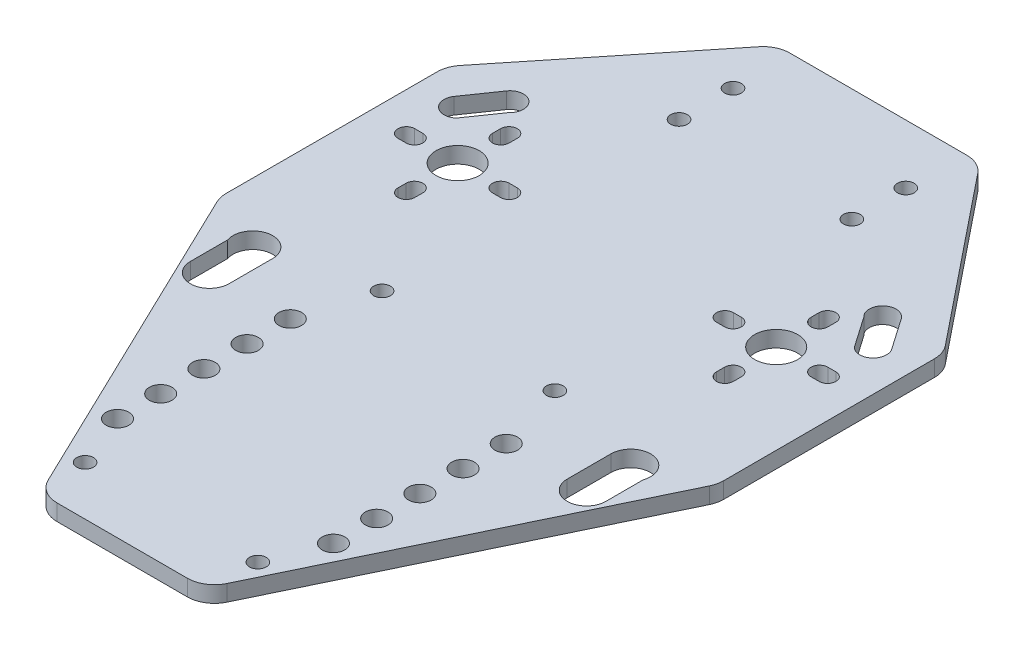
SolidWorks part; units mm, degrees
material "Thornel Mat VMA"
ref_plane "Front Plane" through (0, 0, 0) normal (0, 0, 1) x (1, 0, 0)
ref_plane "Top Plane" through (0, 0, 0) normal (0, 1, 0) x (1, 0, 0)
ref_plane "Right Plane" through (0, 0, 0) normal (1, 0, 0) x (0, 0, -1)
sketch "Sketch1" plane through (0, 0, 0) normal (0, 1, 0) x (1, 0, 0)
  line L0 (0, 0) -> (0, -27.5) construction
  line L1 (0, 0) -> (121.6069, 0) construction
  line L2 (37.5, 0) -> (39, 0) construction
  line L3 (37.5, 1.55) -> (39, 1.55)
  line L4 (37.5, -1.55) -> (39, -1.55)
  line L5 (29.5, -8) -> (29.5, -9.5) construction
  line L6 (31.05, -8) -> (31.05, -9.5)
  line L7 (27.95, -8) -> (27.95, -9.5)
  line L8 (21.5, 0) -> (20, 0) construction
  line L9 (21.5, -1.55) -> (20, -1.55)
  line L10 (21.5, 1.55) -> (20, 1.55)
  line L11 (29.5, 8) -> (29.5, 9.5) construction
  line L12 (27.95, 8) -> (27.95, 9.5)
  line L13 (31.05, 8) -> (31.05, 9.5)
  line L14 (20, -72.5) -> (20, -64.5) construction
  line L19 (-29.5, 8) -> (-29.5, 9.5) construction
  line L20 (-27.95, 8) -> (-27.95, 9.5)
  line L21 (-31.05, 8) -> (-31.05, 9.5)
  line L22 (-21.5, 0) -> (-20, 0) construction
  line L23 (-21.5, -1.55) -> (-20, -1.55)
  line L24 (-21.5, 1.55) -> (-20, 1.55)
  line L25 (-29.5, -8) -> (-29.5, -9.5) construction
  line L26 (-31.05, -8) -> (-31.05, -9.5)
  line L27 (-27.95, -8) -> (-27.95, -9.5)
  line L28 (-37.5, 0) -> (-39, 0) construction
  line L29 (-37.5, 1.55) -> (-39, 1.55)
  line L30 (-37.5, -1.55) -> (-39, -1.55)
  line L31 (-31.3246, -40.5321) -> (-31.3246, -32.4375)
  line L34 (-38.4806, -33.6183) -> (-38.4806, -40.5321)
  line L35 (31.3246, -40.5321) -> (31.3246, -32.4375)
  line L36 (38.4806, -33.6183) -> (38.4806, -40.5321)
  line L37 (-36.8266, 7.1221) -> (-32.8384, 12.8748)
  line L38 (29.5, 0) -> (50.8627, -25.4591) construction
  line L41 (46, 48.4159) -> (-46, 48.4159)
  line L44 (46, 48.4159) -> (46.1488, -91.633)
  line L47 (46.1488, -91.633) -> (-46.1487, -91.584)
  line L50 (-46, 48.4159) -> (-46.1487, -91.584)
  line L53 (-36.5402, 16.1211) -> (-40.5285, 10.3684)
  line L59 (-959, -57) -> (49041, -57) construction
  line L63 (36.8266, 7.1221) -> (32.8384, 12.8748)
  line L64 (36.5402, 16.1211) -> (40.5285, 10.3684)
  circle A0 centre (29.5, 0) radius 4
  arc A1 (37.5, 1.55) -> (37.5, -1.55) centre (37.5, 0) ccw
  arc A2 (39, -1.55) -> (39, 1.55) centre (39, 0) ccw
  arc A3 (31.05, -8) -> (27.95, -8) centre (29.5, -8) ccw
  arc A4 (27.95, -9.5) -> (31.05, -9.5) centre (29.5, -9.5) ccw
  arc A5 (21.5, -1.55) -> (21.5, 1.55) centre (21.5, 0) ccw
  arc A6 (20, 1.55) -> (20, -1.55) centre (20, 0) ccw
  arc A7 (27.95, 8) -> (31.05, 8) centre (29.5, 8) ccw
  arc A8 (31.05, 9.5) -> (27.95, 9.5) centre (29.5, 9.5) ccw
  circle A13 centre (-29.5, 0) radius 4
  arc A14 (-27.95, 8) -> (-31.05, 8) centre (-29.5, 8) cw
  arc A15 (-31.05, 9.5) -> (-27.95, 9.5) centre (-29.5, 9.5) cw
  arc A16 (-21.5, -1.55) -> (-21.5, 1.55) centre (-21.5, 0) cw
  arc A17 (-20, 1.55) -> (-20, -1.55) centre (-20, 0) cw
  arc A18 (-31.05, -8) -> (-27.95, -8) centre (-29.5, -8) cw
  arc A19 (-27.95, -9.5) -> (-31.05, -9.5) centre (-29.5, -9.5) cw
  arc A20 (-37.5, 1.55) -> (-37.5, -1.55) centre (-37.5, 0) cw
  arc A21 (-39, -1.55) -> (-39, 1.55) centre (-39, 0) cw
  circle A22 centre (16, 27.5) radius 1.55
  circle A23 centre (16, -27.5) radius 1.55
  circle A24 centre (-16, -27.5) radius 1.55
  circle A25 centre (-16, 27.5) radius 1.55
  circle A76 centre (-16, 37.5) radius 1.55
  circle A77 centre (16, 37.5) radius 1.55
  circle A78 centre (20, -72.5) radius 2.1
  circle A79 centre (-20, -72.5) radius 2.1
  circle A83 centre (-20, -40.5) radius 2.1
  circle A84 centre (20, -40.5) radius 2.1
  circle A85 centre (20, -64.5) radius 2.1
  circle A86 centre (-20, -64.5) radius 2.1
  circle A87 centre (20, -56.5) radius 2.1
  circle A88 centre (-20, -56.5) radius 2.1
  circle A89 centre (20, -48.5) radius 2.1
  circle A90 centre (-20, -48.5) radius 2.1
  circle A91 centre (-16, -82.5) radius 1.55
  circle A92 centre (16, -82.5) radius 1.55
  arc A93 (-38.4806, -40.5321) -> (-31.3246, -40.5321) centre (-34.9026, -40.5321) ccw
  arc A94 (-31.3246, -32.4375) -> (-38.4806, -33.6183) centre (-35, -32.4375) ccw
  arc A95 (38.4806, -40.5321) -> (31.3246, -40.5321) centre (34.9026, -40.5321) cw
  arc A96 (31.3246, -32.4375) -> (38.4806, -33.6183) centre (35, -32.4375) cw
  arc A103 (-40.5285, 10.3684) -> (-36.8266, 7.1221) centre (-38.4922, 8.9566) ccw
  arc A106 (-36.5402, 16.1211) -> (-32.8384, 12.8748) centre (-34.5039, 14.7093) cw
  arc A107 (36.5402, 16.1211) -> (32.8384, 12.8748) centre (34.5039, 14.7093) ccw
  arc A108 (40.5285, 10.3684) -> (36.8266, 7.1221) centre (38.4922, 8.9566) cw
  point P8 (38.25, 0)
  point P18 (29.5, -8.75)
  point P25 (20.75, 0)
  point P32 (29.5, 8.75)
  point P37 (29.5, 0)
  point P51 (0, 32.5)
  point P55 (-29.5, 8.75)
  point P62 (-20.75, 0)
  point P69 (-29.5, -8.75)
  point P76 (-38.25, 0)
  dimension "D1" = 8
  dimension "D2" = 1.55
  dimension "D4" = 8
  dimension "D5" = 4
  dimension "D6" = 92
  dimension "D7" = 140
  dimension "D8" = 2
  dimension "D9" = 59
  dimension "D10" = 3.1
  dimension "D11" = 40
  dimension "D12" = 27.5
  dimension "D13" = 8
  dimension "D15" = 7
  dimension "D27" = 4.2
  dimension "D28" = 100
  dimension "D3" = 1.5
  dimension "D14" = 35
  dimension "D16" = 7
  dimension "D23" = 50
extrude "Boss-Extrude1" [suppressed] add sketch "Sketch1" along normal blind 3
sketch "草图7" [suppressed] plane through (0, 0, 0) normal (0, 1, 0) x (1, 0, 0)
  line L0 (0, 0) -> (0, -97.058) construction
  line L1 (-27.95, -9.5) -> (-27.95, -8) construction
  line L2 (22.2054, 32.5) -> (-23.2593, 32.5) construction
  line L3 (-31.05, -8) -> (-31.05, -9.5) construction
  line L4 (-37.5, 1.55) -> (-39, 1.55)
  line L5 (-39, -1.55) -> (-37.5, -1.55)
  line L6 (-37.5, 1.55) -> (-39, 1.55)
  line L7 (-39, -1.55) -> (-37.5, -1.55)
  line L8 (-27.95, 8) -> (-27.95, 9.5)
  line L9 (-31.05, 9.5) -> (-31.05, 8)
  line L10 (-27.95, 8) -> (-27.95, 9.5)
  line L11 (-31.05, 9.5) -> (-31.05, 8)
  line L12 (-21.5, -1.55) -> (-20, -1.55)
  line L13 (-20, 1.55) -> (-21.5, 1.55)
  line L14 (-21.5, -1.55) -> (-20, -1.55)
  line L15 (-20, 1.55) -> (-21.5, 1.55)
  line L16 (-27.95, -9.5) -> (-27.95, -8)
  line L17 (-31.05, -8) -> (-31.05, -9.5)
  line L20 (37.5, -1.55) -> (39, -1.55)
  line L21 (39, 1.55) -> (37.5, 1.55)
  line L22 (37.5, -1.55) -> (39, -1.55)
  line L23 (39, 1.55) -> (37.5, 1.55)
  line L24 (27.95, -8) -> (27.95, -9.5)
  line L25 (31.05, -9.5) -> (31.05, -8)
  line L26 (27.95, -8) -> (27.95, -9.5)
  line L27 (31.05, -9.5) -> (31.05, -8)
  line L28 (21.5, 1.55) -> (20, 1.55)
  line L29 (20, -1.55) -> (21.5, -1.55)
  line L30 (21.5, 1.55) -> (20, 1.55)
  line L31 (20, -1.55) -> (21.5, -1.55)
  line L32 (31.05, 8) -> (31.05, 9.5)
  line L33 (27.95, 9.5) -> (27.95, 8)
  line L34 (31.05, 8) -> (31.05, 9.5)
  line L35 (27.95, 9.5) -> (27.95, 8)
  circle A0 centre (29.5, 0) radius 4 construction
  circle A1 centre (29.5, 0) radius 4
  circle A3 centre (-20, -72.5) radius 1.55
  circle A4 centre (-29.5, 0) radius 4
  circle A5 centre (-29.5, 0) radius 4
  circle A6 centre (16, 27.5) radius 1.55
  circle A7 centre (16, 27.5) radius 1.55
  circle A8 centre (-16, 27.5) radius 1.55
  circle A9 centre (-16, 27.5) radius 1.55
  circle A12 centre (16, 37.5) radius 1.55
  circle A13 centre (-16, 37.5) radius 1.55
  circle A14 centre (-16, -27.5) radius 1.55
  circle A15 centre (20, -72.5) radius 1.55
  arc A16 (-31.05, -9.5) -> (-27.95, -9.5) centre (-29.5, -9.5) ccw construction
  arc A18 (-37.5, -1.55) -> (-37.5, 1.55) centre (-37.5, 0) ccw
  arc A19 (-39, 1.55) -> (-39, -1.55) centre (-39, 0) ccw
  arc A20 (-37.5, -1.55) -> (-37.5, 1.55) centre (-37.5, 0) ccw
  arc A21 (-39, 1.55) -> (-39, -1.55) centre (-39, 0) ccw
  arc A23 (-27.95, -8) -> (-31.05, -8) centre (-29.5, -8) ccw construction
  arc A24 (-31.05, 8) -> (-27.95, 8) centre (-29.5, 8) ccw
  arc A25 (-27.95, 9.5) -> (-31.05, 9.5) centre (-29.5, 9.5) ccw
  arc A26 (-31.05, 8) -> (-27.95, 8) centre (-29.5, 8) ccw
  arc A27 (-27.95, 9.5) -> (-31.05, 9.5) centre (-29.5, 9.5) ccw
  arc A28 (-21.5, 1.55) -> (-21.5, -1.55) centre (-21.5, 0) ccw
  arc A29 (-20, -1.55) -> (-20, 1.55) centre (-20, 0) ccw
  arc A30 (-21.5, 1.55) -> (-21.5, -1.55) centre (-21.5, 0) ccw
  arc A31 (-20, -1.55) -> (-20, 1.55) centre (-20, 0) ccw
  arc A32 (-31.05, -9.5) -> (-27.95, -9.5) centre (-29.5, -9.5) ccw
  arc A33 (-27.95, -8) -> (-31.05, -8) centre (-29.5, -8) ccw
  circle A34 centre (16, -27.5) radius 1.55
  arc A36 (37.5, 1.55) -> (37.5, -1.55) centre (37.5, 0) ccw
  arc A37 (39, -1.55) -> (39, 1.55) centre (39, 0) ccw
  arc A38 (37.5, 1.55) -> (37.5, -1.55) centre (37.5, 0) ccw
  arc A39 (39, -1.55) -> (39, 1.55) centre (39, 0) ccw
  arc A40 (31.05, -8) -> (27.95, -8) centre (29.5, -8) ccw
  arc A41 (27.95, -9.5) -> (31.05, -9.5) centre (29.5, -9.5) ccw
  arc A42 (31.05, -8) -> (27.95, -8) centre (29.5, -8) ccw
  arc A43 (27.95, -9.5) -> (31.05, -9.5) centre (29.5, -9.5) ccw
  arc A44 (21.5, -1.55) -> (21.5, 1.55) centre (21.5, 0) ccw
  arc A45 (20, 1.55) -> (20, -1.55) centre (20, 0) ccw
  arc A46 (21.5, -1.55) -> (21.5, 1.55) centre (21.5, 0) ccw
  arc A47 (20, 1.55) -> (20, -1.55) centre (20, 0) ccw
  arc A48 (27.95, 8) -> (31.05, 8) centre (29.5, 8) ccw
  arc A49 (31.05, 9.5) -> (27.95, 9.5) centre (29.5, 9.5) ccw
  arc A50 (27.95, 8) -> (31.05, 8) centre (29.5, 8) ccw
  arc A51 (31.05, 9.5) -> (27.95, 9.5) centre (29.5, 9.5) ccw
  dimension "D4" = 3.1
  dimension "D6" = 20
  dimension "D7" = 5
  dimension "D9" = 3.1
  dimension "D16" = 32
  dimension "D17" = 55
  dimension "D5" = 100
  dimension "D8" = 0
  dimension "D1" = 0
  dimension "D2" = 0
  dimension "D3" = 0
  dimension "D10" = 0
  dimension "D11" = 0
  dimension "D12" = 0
  dimension "D13" = 0
  dimension "D14" = 0
  dimension "D15" = 0
extrude "凸台-拉伸1" add sketch "Sketch1<2>" along normal blind 3 contours L41 L50 L47 L44 A79 A78 A23 A22 A0 A2 L4 A1 L3 A4 L7 A3 L6 A6 L10 A5 L9 A8 L13 A7 L12 A13 L21 A15 L20 A14 L24 A17 L23 A16 region at (0.0029, 0, 21.6938)
sketch "Sketch1<2>" plane through (0, 0, 0) normal (0, 1, 0) x (1, 0, 0) same geometry as "Sketch1"
sketch "草图8" plane through (0, 0, 0) normal (0, 1, 0) x (1, 0, 0)
  line L0 (-11.1069, -100.1389) -> (-60.5812, 2.6993)
  line L1 (-60.5812, 2.6993) -> (-60.5812, -100.1389)
  line L2 (-60.5812, -100.1389) -> (-11.1069, -100.1389)
  line L3 (0, -21.5721) -> (0, 8.1084) construction
  line L4 (60.5812, -100.1389) -> (11.1069, -100.1389)
  line L5 (60.5812, 2.6993) -> (60.5812, -100.1389)
  line L6 (11.1069, -100.1389) -> (60.5812, 2.6993)
  line L7 (-55.5478, 2.6866) -> (-14.4304, 53.8253)
  line L8 (-14.4304, 53.8253) -> (-55.5478, 53.8253)
  line L9 (-55.5478, 53.8253) -> (-55.5478, 2.6866)
  line L10 (55.5478, 53.8253) -> (55.5478, 2.6866)
  line L11 (14.4304, 53.8253) -> (55.5478, 53.8253)
  line L12 (55.5478, 2.6866) -> (14.4304, 53.8253)
extrude "切除-拉伸1" cut sketch "草图8" along normal through all
fillet "圆角1" radius 5 8 edges at (-46.0806, 1.5, 27.4419) (-15.2146, 1.5, 91.6005) (15.2069, 1.5, 91.6166) (46.0806, 1.5, 27.4419) (46.036, 1.5, -14.5166) (18.7797, 1.5, -48.4159) (-18.7797, 1.5, -48.4159) (-46.036, 1.5, -14.5166)
